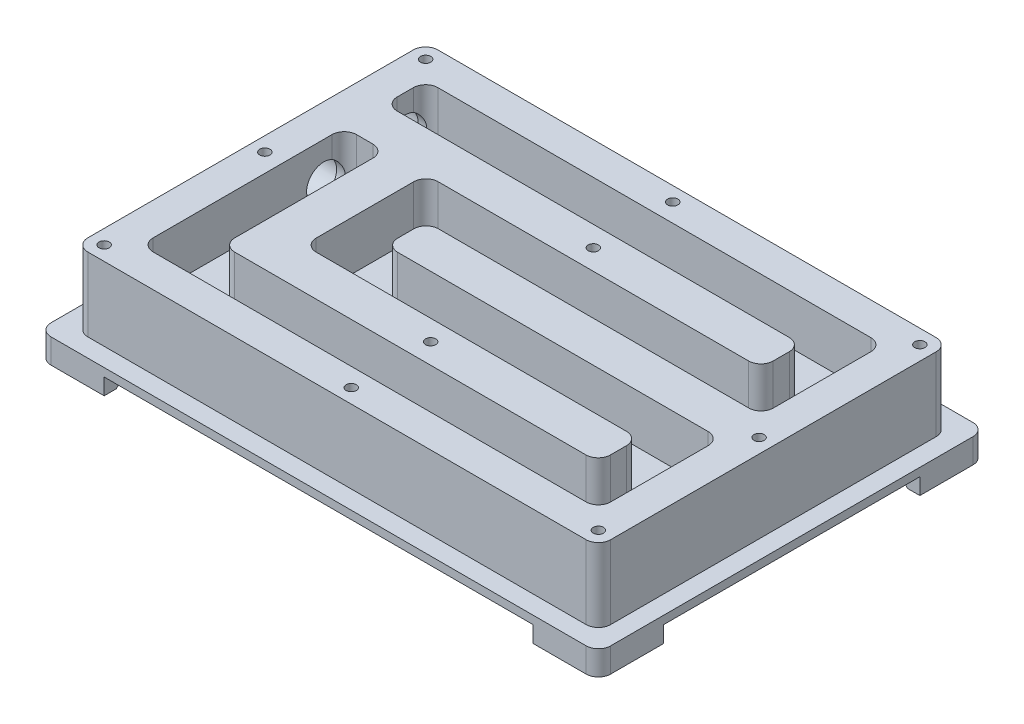
SolidWorks part; units mm, degrees
ref_plane "Front Plane" through (0, 0, 0) normal (0, 0, 1) x (1, 0, 0)
ref_plane "Top Plane" through (0, 0, 0) normal (0, 1, 0) x (1, 0, 0)
ref_plane "Right Plane" through (0, 0, 0) normal (1, 0, 0) x (0, 0, -1)
sketch "Sketch1" plane through (0, 0, 0) normal (0, 1, 0) x (1, 0, 0)
  line L1 (-64, -42.85) -> (64, -42.85)
  line L2 (-64, -42.85) -> (-64, 42.85)
  line L3 (-64, 42.85) -> (64, 42.85)
  line L4 (64, -42.85) -> (64, 42.85)
  line L5 (-64, -42.85) -> (64, 42.85) construction
  line L6 (-64, 42.85) -> (64, -42.85) construction
  point P0 (0, 0)
  dimension "D1" = 85.7
  dimension "D2" = 128
extrude "Boss-Extrude1" add sketch "Sketch1" along normal blind 18
sketch "Sketch2" plane through (0, 18, 0) normal (0, 1, 0) x (1, 0, 0)
  line L0 (-46, 11.9357) -> (-46, -21.8929)
  line L1 (-43, -24.8929) -> (43, -24.8929)
  line L2 (-33, -14.9357) -> (43, -14.9357)
  line L3 (-23, -4.9786) -> (53, -4.9786)
  line L4 (-23, 4.9786) -> (53, 4.9786)
  line L5 (-33, 14.9357) -> (43, 14.9357)
  line L6 (-53, 24.8929) -> (43, 24.8929)
  line L7 (-53, 34.85) -> (53, 34.85)
  line L8 (64, -42.85) -> (64, 42.85) construction
  line L10 (-64, 42.85) -> (-64, -42.85) construction
  line L11 (-64, -42.85) -> (64, -42.85) construction
  line L12 (56, -31.85) -> (56, -7.9786)
  line L14 (-56, 11.9357) -> (-56, -31.85)
  line L15 (-53, -34.85) -> (53, -34.85)
  line L16 (-53, 14.9357) -> (-49, 14.9357)
  line L17 (46, -17.9357) -> (46, -21.8929)
  line L19 (-56, 31.85) -> (-56, 27.8929)
  line L20 (-26, 1.9786) -> (-26, -1.9786)
  line L21 (-36, 11.9357) -> (-36, -11.9357)
  line L22 (46, 21.8929) -> (46, 17.9357)
  line L24 (56, 7.9786) -> (56, 31.85)
  line L25 (64, 42.85) -> (-64, 42.85) construction
  arc A0 (53, 34.85) -> (56, 31.85) centre (53, 31.85) cw
  arc A1 (-53, 24.8929) -> (-56, 27.8929) centre (-53, 27.8929) cw
  arc A3 (53, 4.9786) -> (56, 7.9786) centre (53, 7.9786) ccw
  arc A4 (43, 24.8929) -> (46, 21.8929) centre (43, 21.8929) cw
  arc A5 (46, 17.9357) -> (43, 14.9357) centre (43, 17.9357) cw
  arc A6 (-33, 14.9357) -> (-36, 11.9357) centre (-33, 11.9357) ccw
  arc A7 (-23, 4.9786) -> (-26, 1.9786) centre (-23, 1.9786) ccw
  arc A8 (-26, -1.9786) -> (-23, -4.9786) centre (-23, -1.9786) ccw
  arc A9 (-33, -14.9357) -> (-36, -11.9357) centre (-33, -11.9357) cw
  arc A10 (53, -4.9786) -> (56, -7.9786) centre (53, -7.9786) cw
  arc A11 (43, -14.9357) -> (46, -17.9357) centre (43, -17.9357) cw
  arc A12 (56, -31.85) -> (53, -34.85) centre (53, -31.85) cw
  arc A13 (46, -21.8929) -> (43, -24.8929) centre (43, -21.8929) cw
  arc A14 (-43, -24.8929) -> (-46, -21.8929) centre (-43, -21.8929) cw
  arc A15 (-56, -31.85) -> (-53, -34.85) centre (-53, -31.85) ccw
  arc A16 (-56, 31.85) -> (-53, 34.85) centre (-53, 31.85) cw
  arc A17 (-46, 11.9357) -> (-49, 14.9357) centre (-49, 11.9357) ccw
  arc A18 (-53, 14.9357) -> (-56, 11.9357) centre (-53, 11.9357) ccw
  point P44 (-26, 4.9786)
  point P61 (-46, 14.9357)
  point P64 (-56, 14.9357)
  dimension "D10" = 3
  dimension "D3" = 3
  dimension "D4" = 10
  dimension "D1" = 8
  dimension "D7" = 8
  dimension "D8" = 8
  dimension "D9" = 10
  dimension "D5" = 10
  dimension "D6" = 8
  dimension "D11" = 10
  dimension "D2" = 7
extrude "Cut-Extrude1" cut sketch "Sketch2" against normal blind 12
hole_wizard "M3x0.5 Tapped Hole1" positions "Sketch5" profile "Sketch6" tap size "M3x0.5" standard "ANSI Metric"
sketch "Sketch5" plane through (0, 18, 0) normal (0, 1, 0) x (1, 0, 0)
  line L0 (0, -13.2) -> (0, 13.2) construction
  line L1 (-13.2, 0) -> (13.2, 0) construction
  line L2 (64, 42.85) -> (-64, 42.85) construction
  line L3 (-64, 42.85) -> (-64, -42.85) construction
  line L4 (64, -42.85) -> (64, 42.85) construction
  line L5 (-64, -42.85) -> (64, -42.85) construction
  line L7 (46, 21.8929) -> (46, 17.9357) construction
  line L8 (46, -17.9357) -> (46, -21.8929) construction
  point P0 (-60.5, 39.35)
  point P2 (0, 39.35)
  point P6 (60.5, 39.35)
  point P8 (60.5, 0)
  point P12 (60.5, -39.35)
  point P14 (0, -39.35)
  point P16 (-60.5, -39.35)
  point P18 (-60.5, 0)
  point P29 (0, 19.9143)
  point P31 (0, -19.9143)
  point P41 (46, 19.9143)
  point P46 (46, -19.9143)
  dimension "D1" = 3.5
  dimension "D2" = 3.5
  dimension "D3" = 3.5
  dimension "D4" = 3.5
cosmetic thread "Hole Thread1" parameters "D1"=7, "D2"=3
cosmetic thread "Hole Thread2" parameters "D1"=7, "D2"=3
cosmetic thread "Hole Thread3" parameters "D1"=7, "D2"=3
cosmetic thread "Hole Thread4" parameters "D1"=7, "D2"=3
cosmetic thread "Hole Thread5" parameters "D1"=7, "D2"=3
cosmetic thread "Hole Thread6" parameters "D1"=7, "D2"=3
cosmetic thread "Hole Thread7" parameters "D1"=7, "D2"=3
cosmetic thread "Hole Thread8" parameters "D1"=7, "D2"=3
cosmetic thread "Hole Thread9" parameters "D1"=7, "D2"=3
cosmetic thread "Hole Thread10" parameters "D1"=7, "D2"=3
sketch "Sketch6" plane through (-60.5, 18, -39.35) normal (1, 0, 0) x (0, 0, 1)
  line L0 (0, 0) -> (0, 10.7511)
  line L1 (0, 10.7511) -> (1.25, 10)
  line L2 (1.25, 10) -> (1.25, 0)
  line L5 (1.25, 0) -> (0, 0)
  line L10 (0, 10.7511) -> (-1.25, 10) construction
  line L11 (0, -6.35) -> (0, 107.95) construction
  dimension "Tap Drill Dia." = 2.5
  dimension "Tap Drill Depth" = 10
  dimension "Drill Angle" = 118
sketch "Sketch10" plane through (0, 0, 0) normal (0, -1, 0) x (1, 0, 0)
  line L8 (68.5, -47.35) -> (68.5, 47.35)
  line L9 (68.5, 47.35) -> (-68.5, 47.35)
  line L10 (-68.5, 47.35) -> (-68.5, -47.35)
  line L11 (-68.5, -47.35) -> (68.5, -47.35)
  line L12 (68.5, -47.35) -> (68.5, 47.35)
  line L13 (68.5, 47.35) -> (-68.5, 47.35)
  line L14 (-68.5, 47.35) -> (-68.5, -47.35)
  line L15 (-68.5, -47.35) -> (68.5, -47.35)
  dimension "D1" = 4.5
extrude "Boss-Extrude2" add sketch "Sketch10" along normal blind 6
sketch "Sketch11" plane through (0, -6, 0) normal (0, -1, 0) x (1, 0, 0)
  line L1 (-62.5, -42.875) -> (62.5, -42.875)
  line L2 (-64, -41.375) -> (-64, 41.375)
  line L3 (-62.5, 42.875) -> (62.5, 42.875)
  line L4 (64, -41.375) -> (64, 41.375)
  line L5 (-64, -42.875) -> (64, 42.875) construction
  line L6 (-64, 42.875) -> (64, -42.875) construction
  arc A0 (-62.5, 42.875) -> (-64, 41.375) centre (-64, 42.875) ccw
  arc A1 (64, 41.375) -> (62.5, 42.875) centre (64, 42.875) ccw
  arc A2 (62.5, -42.875) -> (64, -41.375) centre (64, -42.875) ccw
  arc A3 (-64, -41.375) -> (-62.5, -42.875) centre (-64, -42.875) ccw
  point P0 (0, 0)
  dimension "D3" = 3
  dimension "D1" = 85.75
  dimension "D2" = 128
extrude "Cut-Extrude2" cut sketch "Sketch11" against normal blind 4
sketch "Sketch12" plane through (0, -6, 0) normal (0, -1, 0) x (1, 0, 0)
  line L0 (-68.5, 47.35) -> (-68.5, -47.35) construction
  line L1 (-68.5, 31.35) -> (-64, 31.35)
  line L2 (-68.5, 31.35) -> (-68.5, -31.35)
  line L3 (-68.5, -31.35) -> (-64, -31.35)
  line L4 (-64, 31.35) -> (-64, -31.35)
  line L5 (-64, 41.375) -> (-64, -41.375) construction
  line L6 (64, -41.375) -> (64, 41.375) construction
  line L7 (68.5, -47.35) -> (68.5, 47.35) construction
  line L8 (64, 31.35) -> (68.5, 31.35)
  line L9 (64, 31.35) -> (64, -31.35)
  line L10 (64, -31.35) -> (68.5, -31.35)
  line L11 (68.5, 31.35) -> (68.5, -31.35)
  line L12 (68.5, 47.35) -> (-68.5, 47.35) construction
  line L13 (-52.5, 47.35) -> (52.5, 47.35)
  line L14 (-52.5, 47.35) -> (-52.5, 42.875)
  line L15 (-52.5, 42.875) -> (52.5, 42.875)
  line L16 (52.5, 47.35) -> (52.5, 42.875)
  line L17 (62.5, 42.875) -> (-62.5, 42.875) construction
  line L18 (-62.5, -42.875) -> (62.5, -42.875) construction
  line L19 (-52.5, -42.875) -> (52.5, -42.875)
  line L20 (-52.5, -42.875) -> (-52.5, -47.35)
  line L21 (-52.5, -47.35) -> (52.5, -47.35)
  line L22 (52.5, -42.875) -> (52.5, -47.35)
  line L23 (-68.5, -47.35) -> (68.5, -47.35) construction
  point P16 (-64, 0)
  point P18 (64, 0)
  point P35 (0, -42.875)
  point P36 (0, 42.875)
  dimension "D1" = 16
  dimension "D2" = 16
extrude "Cut-Extrude3" cut sketch "Sketch12" against normal up to surface (4 mm away) up to face at (0, -2, 0)
chamfer "Chamfer1" distance 1.5 angle 45 8 edges at (-57.5, -6, -42.875) (-64, -6, -36.3625) (57.5, -6, -42.875) (64, -6, -36.3625) (64, -6, 36.3625) (57.5, -6, 42.875) (-64, -6, 36.3625) (-57.5, -6, 42.875)
fillet "Fillet1" radius 3 8 edges at (68.5, -3, -47.35) (68.5, -3, 47.35) (-68.5, -3, -47.35) (-68.5, -3, 47.35) (-64, 9, 42.85) (64, 9, 42.85) (64, 9, -42.85) (-64, 9, -42.85)
hole_wizard "1/8 NPT Tapped Hole1" positions "Sketch13" profile "Sketch14" size "1/8" standard "ANSI Inch"
sketch "Sketch13" plane through (-64, 0, 0) normal (-1, 0, 0) x (0, 0, 1)
  line L0 (-39.85, 18) -> (-39.85, 0) construction
  line L1 (-31.85, 18) -> (-27.8929, 18) construction
  line L4 (-14.9357, 18) -> (-14.9357, 0) construction
  line L5 (-39.85, 0) -> (39.85, 0) construction
  point P0 (-29.8714, 9)
  point P2 (-9.9357, 9)
  point P7 (-39.85, 9)
  point P10 (-29.8714, 18)
  point P21 (-14.9357, 9)
  dimension "D1" = 5
sketch "Sketch14" plane through (-64, 9, -29.8714) normal (0, 1, 0) x (0, 0, 1)
  line L0 (0, 0) -> (0, 14.1535)
  line L1 (4.2164, 11.62) -> (0, 14.1535)
  line L2 (-4.2164, 11.62) -> (0, 14.1535) construction
  line L3 (4.2164, 11.62) -> (4.2164, 6.92)
  line L4 (4.2164, 6.92) -> (4.9362, 6.92)
  line L5 (4.9362, 6.92) -> (5.1434, 0)
  line L6 (-4.9362, 6.92) -> (-5.1434, 0) construction
  line L7 (5.1434, 0) -> (0, 0)
  line L8 (0, -6.35) -> (0, 107.95) construction
  line L11 (-4.2164, 6.92) -> (-4.9362, 6.92) construction
  dimension "Tap Drill Dia." = 8.4328
  dimension "Tap Drill Depth" = 11.62
  dimension "Thread Dia." = 10.2867
  dimension "Thread Angle" = 3.43
  dimension "Thread Depth" = 6.92
  dimension "Drill Angle" = 118
equation "\"D3@Sketch5\"=\"D2@Sketch5\""
equation "\"D1@Sketch5\"=\"D2@Sketch5\""
equation "\"D4@Sketch5\"=\"D2@Sketch5\""
equation "\"D2@Sketch12\"=\"D1@Sketch12\""
equation "\"D9@Sketch2\"=\"D4@Sketch2\""
equation "\"D5@Sketch2\"=\"D4@Sketch2\""
